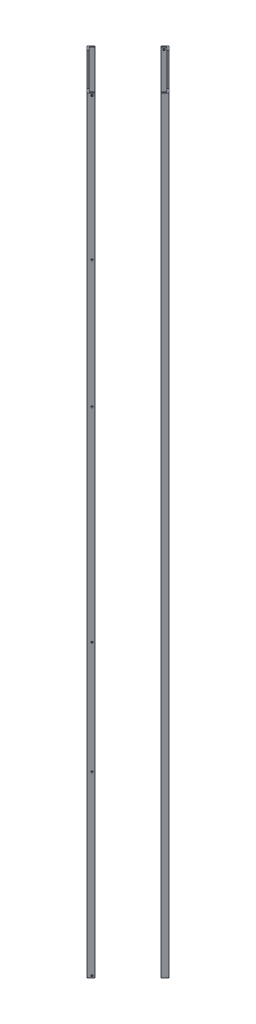
SolidWorks part; units mm, degrees
material "6061-T6 (SS)"
ref_plane "Front Plane" through (0, 0, 0) normal (0, 0, 1) x (1, 0, 0)
ref_plane "Top Plane" through (0, 0, 0) normal (0, 1, 0) x (1, 0, 0)
ref_plane "Right Plane" through (0, 0, 0) normal (1, 0, 0) x (0, 0, -1)
sketch "Sketch2" plane through (0, 0, 0) normal (0, 1, 0) x (1, 0, 0)
  line L0 (0, 94.7743) -> (-8.9803, 85.794)
  line L1 (-8.9803, 85.794) -> (-6.7352, 83.549)
  line L2 (-6.7352, 83.549) -> (0, 90.2842)
  line L3 (0, 90.2842) -> (6.7352, 83.549)
  line L4 (6.7352, 83.549) -> (8.9803, 85.794)
  line L5 (8.9803, 85.794) -> (0, 94.7743)
  line L6 (0, 0) -> (0, 186.644) construction
  line L7 (94.7417, 0.0326) -> (85.7614, 9.0128)
  line L8 (85.7614, 9.0128) -> (83.5164, 6.7678)
  line L9 (83.5164, 6.7678) -> (90.2516, 0.0326)
  line L10 (90.2516, 0.0326) -> (83.5164, -6.7026)
  line L11 (83.5164, -6.7026) -> (85.7614, -8.9477)
  line L12 (85.7614, -8.9477) -> (94.7417, 0.0326)
  line L13 (0, -94.7091) -> (8.9803, -85.7289)
  line L14 (8.9803, -85.7289) -> (6.7352, -83.4838)
  line L15 (6.7352, -83.4838) -> (0, -90.219)
  line L16 (0, -90.219) -> (-6.7352, -83.4838)
  line L17 (-6.7352, -83.4838) -> (-8.9803, -85.7289)
  line L18 (-8.9803, -85.7289) -> (0, -94.7091)
  line L19 (-94.7417, 0.0326) -> (-85.7614, -8.9477)
  line L20 (-85.7614, -8.9477) -> (-83.5164, -6.7026)
  line L21 (-83.5164, -6.7026) -> (-90.2516, 0.0326)
  line L22 (-90.2516, 0.0326) -> (-83.5164, 6.7678)
  line L23 (-83.5164, 6.7678) -> (-85.7614, 9.0128)
  line L24 (-85.7614, 9.0128) -> (-94.7417, 0.0326)
  point P1 (-3.3676, 86.9166)
  point P31 (0, 0.0326)
  dimension "D1" = 127.635
  dimension "D2" = 12.7
  dimension "D3" = 12.7
  dimension "D4" = 3.175
  dimension "D5" = 3.175
  dimension "D7" = 127.635
  dimension "D6" = 4
extrude "Boss-Extrude1" add sketch "Sketch2" along normal blind 1778
sketch "Sketch3" plane through (0, 0, 0) normal (0, -1, 0) x (1, 0, 0)
  circle A0 centre (0, 0) radius 94.7417
sketch "Sketch4" plane through (-47.3546, 0, 47.3546) normal (-0.7071, 0, 0.7071) x (0.7071, 0, 0.7071)
  line L0 (-54.3155, 0) -> (-54.3155, 4.7625)
  line L1 (-54.3155, 1778) -> (-54.3155, 0) construction
  line L2 (-54.3155, 4.7625) -> (-67.0155, 4.7625)
  line L3 (-67.0155, 1778) -> (-67.0155, 0) construction
  line L4 (-67.0155, 0) -> (-54.3155, 0) construction
  circle A0 centre (-59.078, 4.7625) radius 2.0066
  dimension "D2" = 4.0132
  dimension "D3" = 7.9375
  dimension "D4" = 4.7625
  dimension "D1" = 4.7625
extrude "Cut-Extrude1" cut sketch "Sketch4" against normal up to next (3.175 mm away) contours L2 A0 | L2 A0 region at (-89.129, 3.9109, 5.5801) region at (-89.129, 5.6141, 5.5801)
sketch "Sketch5" plane through (-47.3871, 0, -47.3871) normal (-0.7071, 0, -0.7071) x (-0.7071, 0, 0.7071)
  line L0 (-54.3155, 1778) -> (-54.3155, 0) construction
  line L1 (-67.0155, 0) -> (-54.3155, 0)
  line L2 (-67.0155, 0) -> (-67.0155, 4.7625)
  line L3 (-67.0155, 4.7625) -> (-54.3155, 4.7625)
  line L4 (-54.3155, 0) -> (-54.3155, 4.7625)
  line L5 (-67.0155, 1778) -> (-67.0155, 0) construction
  circle A0 centre (-59.078, 4.7625) radius 2.0066
  dimension "D2" = 4.0132
  dimension "D4" = 4.7625
  dimension "D1" = 4.7625
  dimension "D3" = 7.9375
extrude "Cut-Extrude2" cut sketch "Sketch5" against normal up to next (3.175 mm away) contours L3 A0 | L3 A0 region at (-5.6127, 5.6141, -89.1616) region at (-5.6127, 3.9109, -89.1616)
sketch "Sketch6" plane through (47.3871, 0, -47.3871) normal (0.7071, 0, -0.7071) x (-0.7071, 0, -0.7071)
  line L0 (-54.2695, 1778) -> (-54.2695, 0) construction
  line L1 (-66.9695, 0) -> (-54.2695, 0)
  line L2 (-66.9695, 0) -> (-66.9695, 4.7625)
  line L3 (-66.9695, 4.7625) -> (-54.2695, 4.7625)
  line L4 (-54.2695, 0) -> (-54.2695, 4.7625)
  line L5 (-66.9695, 1778) -> (-66.9695, 0) construction
  circle A0 centre (-59.032, 4.7625) radius 2.0066
  dimension "D2" = 4.0132
  dimension "D4" = 4.7625
  dimension "D1" = 4.7625
  dimension "D3" = 7.9375
extrude "Cut-Extrude3" cut sketch "Sketch6" against normal up to next (3.175 mm away) contours L3 A0 | L3 A0 region at (89.129, 5.6141, -5.6452) region at (89.129, 3.9109, -5.6452)
sketch "Sketch7" plane through (47.3546, 0, 47.3546) normal (0.7071, 0, 0.7071) x (0.7071, 0, -0.7071)
  line L0 (-54.2695, 1778) -> (-54.2695, 0) construction
  line L1 (-66.9695, 0) -> (-54.2695, 0)
  line L2 (-66.9695, 0) -> (-66.9695, 4.7625)
  line L3 (-66.9695, 4.7625) -> (-54.2695, 4.7625)
  line L4 (-54.2695, 0) -> (-54.2695, 4.7625)
  line L5 (-66.9695, 1778) -> (-66.9695, 0) construction
  circle A0 centre (-59.032, 4.7625) radius 2.0066
  dimension "D2" = 4.0132
  dimension "D3" = 7.9375
  dimension "D4" = 4.7625
  dimension "D1" = 4.7625
extrude "Cut-Extrude4" cut sketch "Sketch7" against normal up to next (3.175 mm away) contours L3 A0 | L3 A0 region at (5.6127, 5.6141, 89.0965) region at (5.6127, 3.9109, 89.0965)
pattern_linear "LPattern1" count 2 spacing 409.575 along (0, 1, 0) of "Cut-Extrude4", "Cut-Extrude3", "Cut-Extrude1", "Cut-Extrude2"
pattern_linear "LPattern2" count 2 spacing 669.925 along (0, 1, 0) of "Cut-Extrude1", "Cut-Extrude2", "Cut-Extrude3", "Cut-Extrude4"
pattern_linear "LPattern3" count 2 spacing 1143 along (0, 1, 0) of "Cut-Extrude1", "Cut-Extrude2", "Cut-Extrude3", "Cut-Extrude4"
pattern_linear "LPattern4" count 2 spacing 1438.275 along (0, 1, 0) of "Cut-Extrude1", "Cut-Extrude2", "Cut-Extrude3", "Cut-Extrude4"
pattern_linear "LPattern5" count 2 spacing 1768.4775 along (0, 1, 0) of "Cut-Extrude1", "Cut-Extrude2", "Cut-Extrude3", "Cut-Extrude4"
